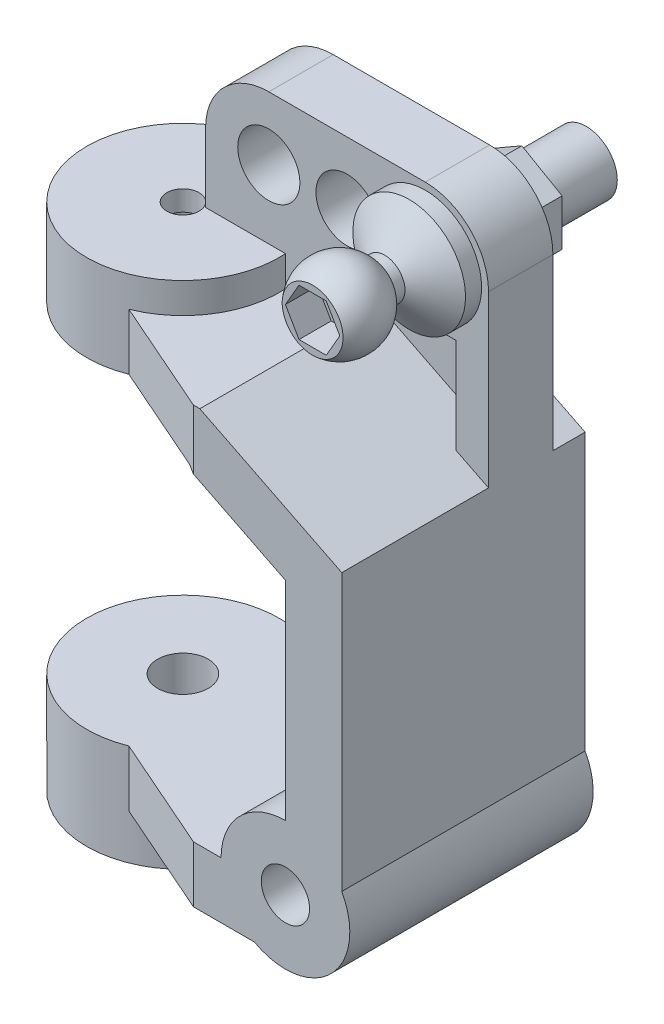
SolidWorks part; units mm, degrees
ref_plane "Front Plane" through (0, 0, 0) normal (0, 0, 1) x (1, 0, 0)
ref_plane "Top Plane" through (0, 0, 0) normal (0, 1, 0) x (1, 0, 0)
ref_plane "Right Plane" through (0, 0, 0) normal (1, 0, 0) x (0, 0, -1)
sketch "Sketch1" plane through (0, 0, 0) normal (0, 0, 1) x (1, 0, 0)
  line L0 (-7.7658, 4.9468) -> (-1.7658, 4.9468)
  line L1 (5.2342, 1.4468) -> (5.2342, -16.4844)
  line L2 (-1.7658, 4.9468) -> (5.2342, 1.4468)
  line L3 (5.2342, -16.4844) -> (-7.7658, -16.4844)
  line L4 (-7.7658, 2.1687) -> (-2.4216, 2.1687)
  line L5 (-2.4216, 2.1687) -> (2.4561, -0.2702)
  line L6 (2.4561, -0.2702) -> (2.4561, -12.5157)
  line L7 (1.2654, -13.7063) -> (-7.7658, -13.7063)
  line L8 (2.4561, -13.7063) -> (-7.7658, -13.7063) construction
  line L9 (2.4561, -0.2702) -> (2.4561, -13.7063) construction
  line L10 (-7.7658, 4.9468) -> (-7.7658, 2.1687)
  line L11 (-7.7658, -13.7063) -> (-7.7658, -16.4844)
  circle A0 centre (2.4561, -13.7063) radius 1.1906
  circle A1 centre (2.4561, -13.7063) radius 3.175
  dimension "D6" = 2.3813
  dimension "D7" = 6.35
  dimension "D1" = 13
  dimension "D2" = 21.4312
  dimension "D3" = 7
  dimension "D5" = 2.7781
extrude "Boss-Extrude1" add sketch "Sketch1" along normal blind 12 contours A1 L1 L2 L0 L10 L4 L5 L6 | L1 A1 L6 A0 L7 L3 | L6 A1 L7 A0 | L1 A1 | L3 A1 | A1 L7 L11 L3 region at (-4.7658, 4.7319, 0) region at (5.3938, -13.7063, 0) region at (5.15, -13.7063, 0) region at (0.9707, -12.221, 0) region at (2.4561, -16.6441, 0) region at (-3.9917, -15.1417, 0)
sketch "Sketch3" plane through (0, -16.4844, 0) normal (0, -1, 0) x (1, 0, 0)
  line L0 (-7.7658, 9.5) -> (-2.081, 12)
  line L1 (-7.7658, 12) -> (-7.7658, 0) construction
  line L2 (0.919, 12) -> (-7.7658, 12) construction
  line L3 (-2.081, 12) -> (-7.7658, 12)
  line L4 (-7.7658, 12) -> (-7.7658, 9.5)
  line L5 (0.919, 12) -> (0.919, 0) construction
  dimension "D1" = 2.5
  dimension "D2" = 3
extrude "Cut-Extrude1" cut sketch "Sketch3" against normal through all
sketch "Sketch4" plane through (0, 4.9468, 0) normal (0, 1, 0) x (1, 0, 0)
  line L0 (-14.2658, -5.0841) -> (-14.2658, 0.3364) construction
  line L2 (5.2342, -12) -> (5.2342, 0) construction
  circle A0 centre (-9.5158, -5.0841) radius 4.75
  circle A1 centre (-9.5158, -5.0841) radius 1.25
  dimension "D2" = 9.5
  dimension "D3" = 2.5
  dimension "D1" = 19.5
extrude "Boss-Extrude2" add sketch "Sketch4" along normal blind 1.5 and the other way up to surface (2.7781 mm away) contours A1 | A0 region at (-9.5158, 4.9468, 5.0841) other way up to face at (-5.0937, 2.1687, 5.3376)
sketch "Sketch5" plane through (0, -13.7063, 0) normal (0, 1, 0) x (1, 0, 0)
  line L0 (-5.3982, -7.4523) -> (-4.4052, -5.7257)
  line L1 (-4.7658, -5.0841) -> (-4.2339, -5.0841) construction
  line L2 (-4.2339, -5.0841) -> (-4.2339, -2.0182) construction
  line L3 (-8.2658, -5.0841) -> (-8.2658, -4.9815) construction
  line L4 (-5.3982, -2.716) -> (-4.4052, -4.4426)
  circle A0 centre (-9.5158, -5.0841) radius 4.75
  circle A1 centre (-9.5158, -5.0841) radius 1.25
  arc A2 (-4.4052, -4.4426) -> (-4.4052, -5.7257) centre (-5.5207, -5.0841) cw
  circle A3 centre (-9.5158, -5.0841) radius 1.25 construction
  arc A4 (-7.7658, -0.6682) -> (-7.7658, -9.5) centre (-9.5158, -5.0841) ccw construction
  line M1 (-7.7658, 0) -> (-7.7658, -9.5)
  line M5 (-0.7189, 0) -> (-7.7658, 0)
extrude "Boss-Extrude3" add sketch "Sketch5" against normal blind 5 contours A0 A1 M5 M1 | A0 M1 M5 | A2 L4 A0 L0 region at (-4.6406, -13.7063, 5.0841) region at (-6.5259, -13.7063, 5.0841) region at (-14.1507, -13.7063, 5.0841)
sketch "Sketch6" plane through (0, -18.7063, 0) normal (0, -1, 0) x (1, 0, 0)
  line L0 (-8.2658, 5.0841) -> (-4.2339, 5.0841) construction
  circle A0 centre (-6.2498, 5.0841) radius 0.95
  circle A1 centre (-9.5158, 5.0841) radius 1.25 construction
  arc A2 (-4.4052, 4.4426) -> (-4.4052, 5.7257) centre (-5.5207, 5.0841) ccw construction
  dimension "D1" = 1.9
extrude "Cut-Extrude2" cut sketch "Sketch6" against normal blind 3
sketch "Sketch8" plane through (0, 6.4468, 0) normal (0, 1, 0) x (1, 0, 0)
  circle A0 centre (-9.5158, -5.0841) radius 0.7937
  circle A1 centre (-9.5158, -5.0841) radius 1.25
  dimension "D1" = 1.5875
extrude "Boss-Extrude4" add sketch "Sketch8" against normal blind 1
ref_plane "Plane1" through (0, 0, 2.3813) normal (0, 0, -1) x (-1, 0, 0)
sketch "Sketch9" plane through (0, 0, 2.3813) normal (0, 0, -1) x (-1, 0, 0)
  line L0 (5.9714, 2.1687) -> (-2.4561, -2.0451)
  line L1 (2.4216, 2.1687) -> (7.7658, 2.1687) construction
  line L2 (-2.4561, -0.2702) -> (-2.4561, -10.5313) construction
  line L3 (2.081, 1.9984) -> (-2.4561, -0.2702) construction
  line L4 (-2.4561, -0.2702) -> (-2.4561, -10.5313) construction
  line L5 (7.7658, -13.7063) -> (2.081, -13.7063) construction
  line L6 (5.9714, 2.1687) -> (2.4216, 2.1687)
  line L7 (4.6422, -13.7063) -> (-2.4561, -10.1564)
  line L8 (-2.4561, -5.4007) -> (0, -5.4007) construction
  line L9 (2.4216, 2.1687) -> (-2.4561, -0.2702)
  line L10 (-2.4561, -0.2702) -> (-2.4561, -2.0451)
  line L11 (4.6422, -13.7063) -> (0, -13.7063)
  line L12 (0, -13.7063) -> (-2.4561, -11.5358)
  line L13 (-2.4561, -10.1564) -> (-2.4561, -11.5358)
  arc A0 (0.7189, -13.7063) -> (-2.4561, -10.5313) centre (-2.4561, -13.7063) ccw construction
  dimension "D1" = 1.5875
  dimension "D2" = 26.57
extrude "Boss-Extrude5" add sketch "Sketch9" against normal blind 0.625
ref_plane "Plane2" through (0, 0, 1.5875) normal (0, 0, -1) x (-1, 0, 0)
sketch "Sketch11" plane through (0, 0, 1.5875) normal (0, 0, -1) x (-1, 0, 0)
  line L0 (-5.2342, 1.4468) -> (-5.2342, 9.827)
  line L1 (-2.1144, 12.9468) -> (5.6023, 12.9468)
  line L2 (8.7221, 9.827) -> (8.7221, 6.4468)
  line L3 (10.3096, 6.4468) -> (8.7221, 6.4468) construction
  line L4 (-5.2342, 1.4468) -> (1.7658, 4.9468)
  line L5 (1.7658, 4.9468) -> (8.7221, 4.9468)
  line L6 (8.7221, 4.9468) -> (8.7221, 6.4468)
  line L7 (-2.1144, 11.3593) -> (5.6023, 11.3593) construction
  line L8 (7.1346, 9.827) -> (7.1346, 8.7482) construction
  line L9 (3.2762, 9.827) -> (3.2762, 8.3732) construction
  line L10 (4.07, 9.827) -> (4.07, 8.3732) construction
  line L11 (5.6023, 8.2947) -> (1.7439, 8.2947) construction
  line L14 (1.7439, 11.3593) -> (1.7439, 11.9945) construction
  line L15 (-2.1144, 8.2947) -> (1.7439, 8.2947) construction
  arc A0 (8.7221, 9.827) -> (5.6023, 12.9468) centre (5.6023, 9.827) ccw
  arc A1 (-2.1144, 12.9468) -> (-5.2342, 9.827) centre (-2.1144, 9.827) ccw
  circle A2 centre (5.6023, 9.827) radius 1.5323
  circle A3 centre (1.7439, 9.827) radius 1.5323
  circle A4 centre (-2.1144, 9.827) radius 1.5323
  dimension "D1" = 1.5875
  dimension "D3" = 8
  dimension "D4" = 0.7937
extrude "Boss-Extrude6" add sketch "Sketch11" against normal blind 3.175
sketch "Sketch14" plane through (0, 0, 4.7625) normal (0, 0, 1) x (1, 0, 0)
  line L0 (3.6342, 2.2468) -> (3.6342, 6.9468)
  line L1 (5.2342, 1.4468) -> (-1.7658, 4.9468) construction
  line L2 (3.6342, 6.9468) -> (-2.3658, 6.9468)
  line L3 (-2.3658, 6.9468) -> (-2.3658, 4.9468)
  line L4 (-1.7658, 4.9468) -> (-4.7767, 4.9468) construction
  line L5 (-2.3658, 4.9468) -> (-1.7658, 4.9468)
  line L6 (-1.7658, 4.9468) -> (3.6342, 2.2468)
  line L7 (5.2342, 9.827) -> (5.2342, 1.4468) construction
  dimension "D1" = 1.6
  dimension "D2" = 2
  dimension "D3" = 6
extrude "Cut-Extrude3" cut sketch "Sketch14" against normal blind 1.5875
ref_axis "Axis1" through (2.1144, 9.827, 4.7625) along (0, 0, -1)
ref_plane "Plane3" through (2.1144, 0, 0) normal (1, 0, 0) x (0, 0, -1)
sketch "Sketch12" plane through (2.1144, 0, 0) normal (1, 0, 0) x (0, 0, -1)
  line L0 (-1.5875, 9.827) -> (3.175, 9.827)
  line L1 (-4.7625, 9.827) -> (-1.5875, 9.827) construction
  line L2 (3.175, 9.827) -> (3.175, 11.3593)
  line L3 (3.175, 11.3593) -> (-1.5875, 11.3593)
  line L4 (-1.5875, 11.3593) -> (-4.7625, 11.3593)
  line L5 (-4.7625, 11.3593) -> (-4.7625, 12.6051)
  line L6 (-4.7625, 12.6051) -> (-5.5562, 12.6051)
  line L7 (-5.5562, 12.6051) -> (-6.7625, 10.827)
  line L8 (-6.7625, 10.827) -> (-7.2625, 10.827)
  line L9 (-10.3187, 11.327) -> (-10.3187, 9.827)
  line L10 (-1.5875, 9.827) -> (-10.3187, 9.827)
  line L11 (-4.7625, 9.827) -> (-4.7625, 1.4468) construction
  line L12 (-8.9954, 11.827) -> (-7.5799, 11.827) construction
  line L13 (-4.7625, 12.6051) -> (-4.7625, 11.3593)
  arc A0 (-7.2625, 10.827) -> (-10.3187, 11.327) centre (-8.9954, 9.8256) ccw
  dimension "D1" = 4.7625
  dimension "D2" = 5.5562
  dimension "D3" = 2.7781
  dimension "D4" = 0.7937
  dimension "D5" = 1
  dimension "D6" = 2
  dimension "D7" = 1.5
  dimension "D8" = 2
  dimension "D9" = 2.5
revolve "Revolve1" add sketch "Sketch12" angle 360 about axis through (2.1144, 9.827, 4.7625) along (0, 0, -1) region at (2.1144, 10.7053, 3.8206)
sketch "Sketch13" plane through (0, 0, 1.5875) normal (0, 0, -1) x (-1, 0, 0)
  line L0 (-5.2342, 9.827) -> (-5.2342, 1.4468) construction
  line L1 (-0.13, 10.9727) -> (-2.1144, 12.1184)
  line L2 (-2.1144, 12.1184) -> (-4.0988, 10.9727)
  line L3 (-4.0988, 10.9727) -> (-4.0988, 8.6813)
  line L4 (-4.0988, 8.6813) -> (-2.1144, 7.5357)
  line L5 (-2.1144, 7.5357) -> (-0.13, 8.6813)
  line L6 (-0.13, 8.6813) -> (-0.13, 10.9727)
  circle A0 centre (-2.1144, 9.827) radius 1.5323
  circle A1 centre (-2.1144, 9.827) radius 1.9844 construction
  dimension "D1" = 3.9688
extrude "Boss-Extrude7" add sketch "Sketch13" along normal blind 1.5875
sketch "Sketch15" plane through (0, 0, 10.3187) normal (0, 0, 1) x (1, 0, 0)
  line L1 (3.4553, 9.827) -> (2.7849, 10.9883)
  line L2 (2.7849, 10.9883) -> (1.4439, 10.9883)
  line L3 (1.4439, 10.9883) -> (0.7735, 9.827)
  line L4 (0.7735, 9.827) -> (1.4439, 8.6657)
  line L5 (1.4439, 8.6657) -> (2.7849, 8.6657)
  line L6 (2.7849, 8.6657) -> (3.4553, 9.827)
  circle A0 centre (2.1144, 9.827) radius 1.1613 construction
extrude "Cut-Extrude4" cut sketch "Sketch15" against normal blind 1.5875
ref_point "Point1"
